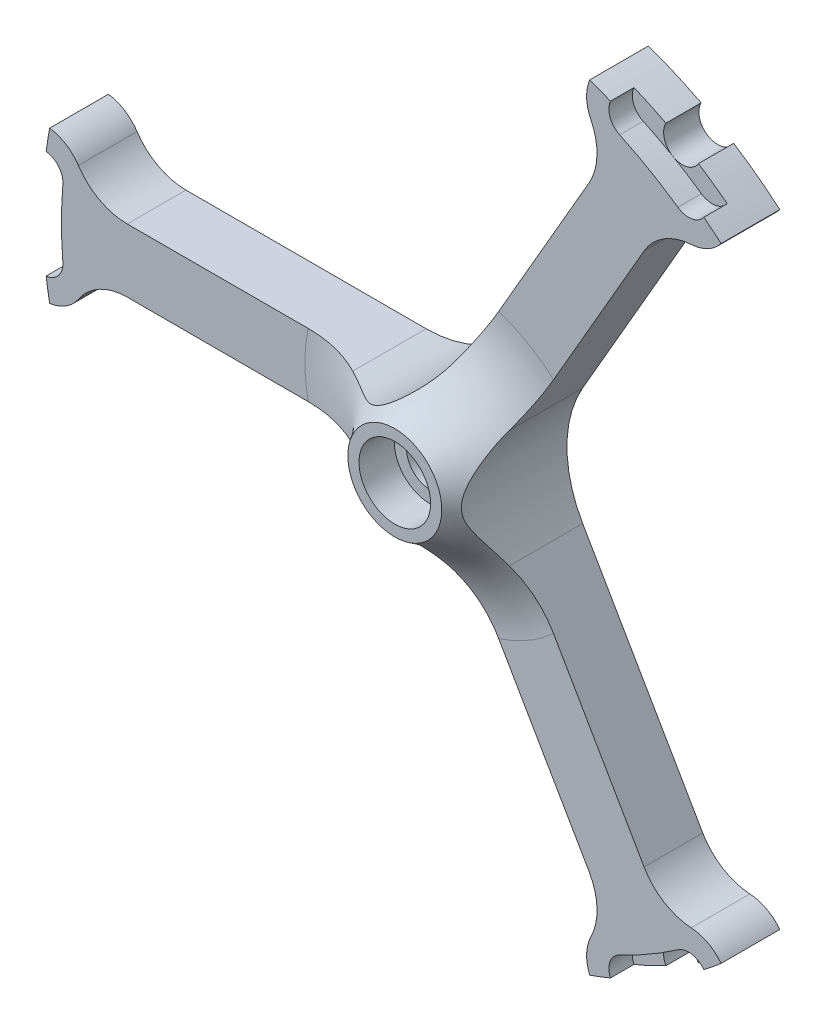
SolidWorks part; units mm, degrees
ref_plane "Plan de face" through (0, 0, 0) normal (0, 0, 1) x (1, 0, 0)
ref_plane "Plan de dessus" through (0, 0, 0) normal (0, 1, 0) x (1, 0, 0)
ref_plane "Plan de droite" through (0, 0, 0) normal (1, 0, 0) x (0, 0, -1)
sketch "Esquisse1" plane through (0, 0, 0) normal (0, 0, 1) x (1, 0, 0)
  line L19 (-1000, 0) -> (49000, 0) construction
  line L21 (-27.7888, 2.7) -> (-7.3323, 2.7)
  line L23 (-27.7888, -2.7) -> (-7.3323, -2.7)
  line L33 (16.2327, 22.7158) -> (6.0044, 5)
  line L34 (11.5561, 25.4158) -> (1.3279, 7.7)
  line L35 (11.5561, -25.4158) -> (1.3279, -7.7)
  line L36 (16.2327, -22.7158) -> (6.0044, -5)
  arc A0 (-34.3972, 6.4678) -> (-34.6976, 4.5906) centre (0, 0) ccw
  arc A7 (-33.2771, 2.8629) -> (-34.6976, 4.5906) centre (-34.8712, 3) ccw
  arc A8 (-33.2771, -2.8629) -> (-34.6976, -4.5906) centre (-34.8712, -3) cw
  arc A12 (-33.2771, 2.8629) -> (-33.2771, -2.8629) centre (0, 0) ccw
  arc A13 (-31.9549, 4.9353) -> (-34.3972, 6.4678) centre (-34.8712, 3) ccw
  arc A14 (-31.9549, -4.9353) -> (-34.3972, -6.4678) centre (-34.8712, -3) cw
  arc A15 (-34.6976, -4.5906) -> (-34.3972, -6.4678) centre (0, 0) ccw
  arc A16 (-27.7888, -2.7) -> (-31.9549, -4.9353) centre (-27.7888, -7.7) ccw
  arc A17 (-27.7888, 2.7) -> (-31.9549, 4.9353) centre (-27.7888, 7.7) cw
  arc A48 (22.7998, 26.555) -> (21.3244, 27.7538) centre (0, 0) ccw
  arc A49 (19.1178, 27.3874) -> (21.3244, 27.7538) centre (20.0337, 28.6993) ccw
  arc A50 (14.1592, 30.2502) -> (13.3733, 32.3443) centre (14.8375, 31.6993) cw
  arc A51 (19.1178, 27.3874) -> (14.1592, 30.2502) centre (0, 0) ccw
  arc A52 (20.2516, 25.2061) -> (22.7998, 26.555) centre (20.0337, 28.6993) ccw
  arc A53 (11.7034, 30.1414) -> (11.5974, 33.0227) centre (14.8375, 31.6993) cw
  arc A54 (13.3733, 32.3443) -> (11.5974, 33.0227) centre (0, 0) ccw
  arc A55 (11.5561, 25.4158) -> (11.7034, 30.1414) centre (7.226, 27.9158) ccw
  arc A56 (16.2327, 22.7158) -> (20.2516, 25.2061) centre (20.5628, 20.2158) cw
  arc A57 (11.5974, -33.0227) -> (13.3733, -32.3443) centre (0, 0) ccw
  arc A58 (14.1592, -30.2502) -> (13.3733, -32.3443) centre (14.8375, -31.6993) ccw
  arc A59 (19.1178, -27.3874) -> (21.3244, -27.7538) centre (20.0337, -28.6993) cw
  arc A60 (14.1592, -30.2502) -> (19.1178, -27.3874) centre (0, 0) ccw
  arc A61 (11.7034, -30.1414) -> (11.5974, -33.0227) centre (14.8375, -31.6993) ccw
  arc A62 (20.2516, -25.2061) -> (22.7998, -26.555) centre (20.0337, -28.6993) cw
  arc A63 (21.3244, -27.7538) -> (22.7998, -26.555) centre (0, 0) ccw
  arc A64 (16.2327, -22.7158) -> (20.2516, -25.2061) centre (20.5628, -20.2158) ccw
  arc A65 (11.5561, -25.4158) -> (11.7034, -30.1414) centre (7.226, -27.9158) cw
  arc A66 (-7.3323, -2.7) -> (1.3279, -7.7) centre (-7.3323, -12.7) cw
  arc A67 (6.0044, -5) -> (6.0044, 5) centre (14.6647, 0) cw
  arc A68 (1.3279, 7.7) -> (-7.3323, 2.7) centre (-7.3323, 12.7) cw
  point P38 (0, 0)
  point P50 (3.1177, 0)
  point P55 (0, 0)
  point P56 (0, 0)
  point P80 (0, 0)
  dimension "D1" = 70
  dimension "D3" = 3
  dimension "D2" = 3.2
  dimension "D4" = 5
  dimension "D5" = 10
extrude "Boss.-Extru.1" add sketch "Esquisse1" along normal blind 5
sketch "Esquisse7" plane through (0, 0, 0) normal (0, 0, -1) x (-1, 0, 0)
  line L0 (-1000, 0) -> (49000, 0) construction
  arc A0 (34.6976, -4.5906) -> (34.6976, 4.5906) centre (0, 0) ccw
  arc A2 (33.2771, -2.8629) -> (33.2771, 2.8629) centre (0, 0) ccw
  arc A4 (34.9634, 1.5996) -> (34.9634, -1.5996) centre (35, 0) ccw
  arc A5 (34.6976, 4.5906) -> (33.2771, 2.8629) centre (34.8712, 3) ccw
  arc A6 (33.2771, -2.8629) -> (33.2771, 2.8629) centre (0, 0) ccw construction
  arc A7 (34.6976, -4.5906) -> (33.2771, -2.8629) centre (34.8712, -3) cw
  arc A8 (-21.3244, -27.7538) -> (-13.3733, -32.3443) centre (0, 0) ccw
  arc A9 (-19.1178, -27.3874) -> (-14.1592, -30.2502) centre (0, 0) ccw
  arc A10 (-16.0964, -31.079) -> (-18.867, -29.4794) centre (-17.5, -30.3109) ccw
  arc A11 (-13.3733, -32.3443) -> (-14.1592, -30.2502) centre (-14.8375, -31.6993) ccw
  arc A12 (-21.3244, -27.7538) -> (-19.1178, -27.3874) centre (-20.0337, -28.6993) cw
  arc A13 (-13.3733, 32.3443) -> (-21.3244, 27.7538) centre (0, 0) ccw
  arc A14 (-14.1592, 30.2502) -> (-19.1178, 27.3874) centre (0, 0) ccw
  arc A15 (-18.867, 29.4794) -> (-16.0964, 31.079) centre (-17.5, 30.3109) ccw
  arc A16 (-21.3244, 27.7538) -> (-19.1178, 27.3874) centre (-20.0337, 28.6993) ccw
  arc A17 (-13.3733, 32.3443) -> (-14.1592, 30.2502) centre (-14.8375, 31.6993) cw
  point P36 (0, 0)
  arc M44 (34.6976, -4.5906) -> (33.2771, -2.8629) centre (34.8712, -3) cw
  arc M45 (33.2771, -2.8629) -> (33.2771, 2.8629) centre (0, 0) ccw
  arc M46 (33.2771, 2.8629) -> (34.6976, 4.5906) centre (34.8712, 3) cw
  arc M56 (-13.3733, 32.3443) -> (-14.1592, 30.2502) centre (-14.8375, 31.6993) cw
  arc M57 (-14.1592, 30.2502) -> (-19.1178, 27.3874) centre (0, 0) ccw
  arc M58 (-19.1178, 27.3874) -> (-21.3244, 27.7538) centre (-20.0337, 28.6993) cw
  arc M68 (-21.3244, -27.7538) -> (-19.1178, -27.3874) centre (-20.0337, -28.6993) cw
  arc M69 (-19.1178, -27.3874) -> (-14.1592, -30.2502) centre (0, 0) ccw
  arc M70 (-14.1592, -30.2502) -> (-13.3733, -32.3443) centre (-14.8375, -31.6993) cw
  dimension "D1" = 3.2
  dimension "D3" = 3.2
  dimension "D4" = 70
  dimension "D2" = 3
extrude "Boss.-Extru.5" add sketch "Esquisse7" against normal blind 3 contours A4 A0 A2 M46 | A4 A0 M45 M44 | A10 A8 A9 M70 | A10 A8 M69 M68 | A15 A13 M57 M56 | A15 A13 A14 M58 region at (-34.0862, -2.7129, 0) region at (-34.0862, 2.7129, 0) region at (19.3926, -28.1631, 0) region at (14.6937, -30.876, 0) region at (14.6937, 30.876, 0) region at (19.3926, 28.1631, 0)
sketch "Esquisse4" plane through (0, 0, 5) normal (0, 0, 1) x (1, 0, 0)
  circle A1 centre (0, 0) radius 4
  dimension "D1" = 8
extrude "Boss.-Extru.3" add sketch "Esquisse4" along normal blind 5
sketch "Esquisse5" plane through (0, 0, 10) normal (0, 0, 1) x (1, 0, 0)
  circle A0 centre (0, 0) radius 3.05
  dimension "D1" = 6.1
extrude "Enlèv. mat.-Extru.2" cut sketch "Esquisse5" against normal blind 3
fillet "Congé1" radius 10 1 edges at (4, 0, 5)
sketch "Esquisse6" plane through (0, 0, 7) normal (0, 0, 1) x (1, 0, 0)
  circle A0 centre (0, 0) radius 2
  dimension "D1" = 4
extrude "Enlèv. mat.-Extru.3" cut sketch "Esquisse6" against normal up to next
